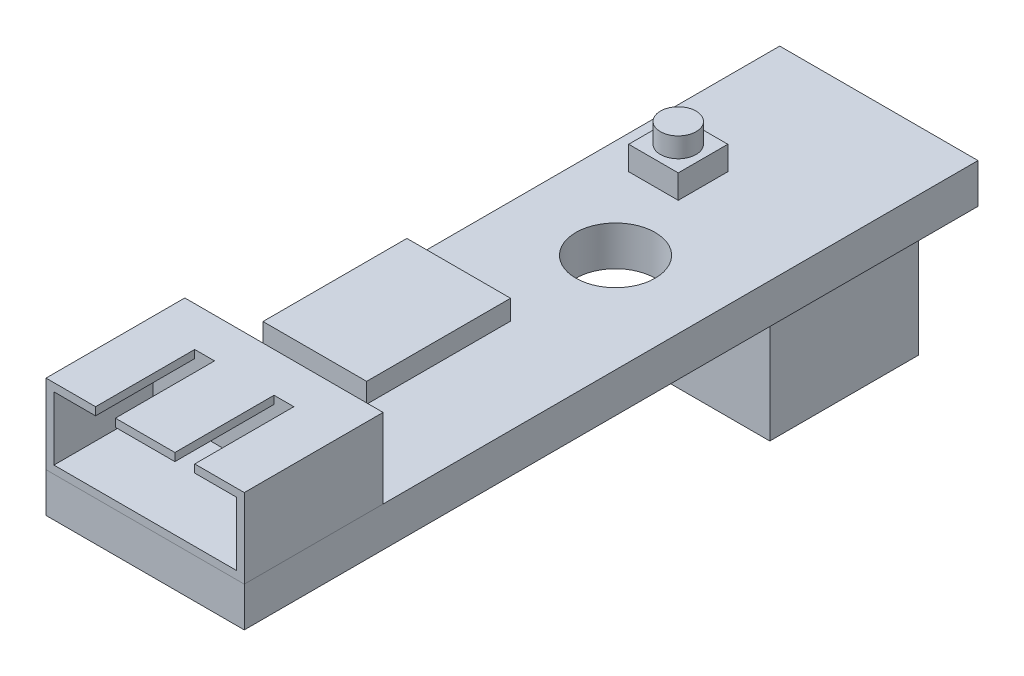
SolidWorks part; units mm, degrees
ref_plane "前视基准面" through (0, 0, 0) normal (0, 0, 1) x (1, 0, 0)
ref_plane "上视基准面" through (0, 0, 0) normal (0, 1, 0) x (1, 0, 0)
ref_plane "右视基准面" through (0, 0, 0) normal (1, 0, 0) x (0, 0, -1)
sketch "草图1" plane through (0, 0, 0) normal (0, 1, 0) x (1, 0, 0)
  line L1 (-5, 18.5) -> (5, 18.5)
  line L2 (-5, 18.5) -> (-5, -18.5)
  line L3 (-5, -18.5) -> (5, -18.5)
  line L4 (5, 18.5) -> (5, -18.5)
  line L5 (-5, 18.5) -> (5, -18.5) construction
  line L6 (-5, -18.5) -> (5, 18.5) construction
  point P0 (0, 0)
  dimension "D1" = 37
  dimension "D2" = 10
extrude "凸台-拉伸1" add sketch "草图1" along normal blind 2
sketch "草图2" plane through (0, 2, 0) normal (0, 1, 0) x (1, 0, 0)
  line L0 (-5, 18.5) -> (-5, -18.5) construction
  line L1 (-5, -11.5) -> (5, -11.5)
  line L2 (-5, -11.5) -> (-5, -18.5)
  line L3 (-5, -18.5) -> (5, -18.5)
  line L4 (5, -11.5) -> (5, -18.5)
  dimension "D1" = 7
extrude "凸台-拉伸2" add sketch "草图2" along normal blind 4 separate body
sketch "草图3" plane through (0, 0, 18.5) normal (0, 0, 1) x (1, 0, 0)
  line L4 (-5, 2) -> (5, 2)
  line L5 (5, 2) -> (5, 6)
  line L6 (5, 6) -> (-5, 6)
  line L7 (-5, 6) -> (-5, 2)
  line L8 (-5, 2) -> (5, 2) construction
  line L9 (5, 2) -> (5, 6) construction
  line L10 (5, 6) -> (-5, 6) construction
  line L11 (-5, 6) -> (-5, 2) construction
  line L12 (0, 5.6) -> (0, 7.429) construction
  line L13 (1.5, 6) -> (1.5, 5.6)
  line L14 (-2.5, 6) -> (-1.5, 6)
  line L15 (-2.5, 6) -> (-2.5, 5.6)
  line L16 (-4.6, 2.4) -> (4.6, 2.4)
  line L17 (4.6, 2.4) -> (4.6, 5.6)
  line L18 (4.6, 5.6) -> (-4.6, 5.6)
  line L19 (-4.6, 5.6) -> (-4.6, 2.4)
  line L20 (-4.6, 2.4) -> (4.6, 2.4)
  line L21 (4.6, 2.4) -> (4.6, 5.6)
  line L22 (4.6, 5.6) -> (2.5, 5.6)
  line L23 (-4.6, 5.6) -> (-4.6, 2.4)
  line L24 (-2.5, 5.6) -> (-1.5, 5.6) construction
  line L25 (-1.5, 6) -> (-1.5, 5.6)
  line L26 (2.5, 6) -> (2.5, 5.6)
  line L27 (2.5, 6) -> (1.5, 6)
  line L28 (-1.5, 5.6) -> (-2.5, 5.6) construction
  line L29 (-2.5, 5.6) -> (-4.6, 5.6)
  line L30 (2.5, 5.6) -> (1.5, 5.6) construction
  line L31 (1.5, 5.6) -> (-1.5, 5.6)
  dimension "D3" = 3
  dimension "D4" = 1
  dimension "D1" = 0
  dimension "D2" = 0.4
extrude "切除-拉伸1" cut sketch "草图3" against normal blind 5
sketch "草图4" plane through (0, 0, 0) normal (0, -1, 0) x (1, 0, 0)
  line L0 (0, 18.5) -> (0, -18.5) construction
  line L1 (-5, 18.5) -> (5, 18.5) construction
  line L2 (5, -18.5) -> (-5, -18.5) construction
  circle A0 centre (0, -5.221) radius 2
  dimension "D1" = 4
extrude "切除-拉伸2" cut sketch "草图4" against normal blind 5
sketch "草图5" plane through (0, 0, 0) normal (0, -1, 0) x (1, 0, 0)
  line L0 (5, 18.5) -> (5, -18.5) construction
  line L1 (-2, -10) -> (3, -10)
  line L2 (-3, -11) -> (-3, -17.5)
  line L3 (-3, -17.5) -> (3, -17.5)
  line L4 (3, -10) -> (3, -17.5)
  line L5 (5, -18.5) -> (-5, -18.5) construction
  line L6 (-3, -11) -> (-2, -10)
  point P0 (-3, -10)
  dimension "D1" = 6
  dimension "D2" = 7.5
  dimension "D3" = 2
  dimension "D4" = 1
extrude "凸台-拉伸3" add sketch "草图5" along normal blind 7
sketch "草图6" plane through (0, 2, 0) normal (0, 1, 0) x (1, 0, 0)
  line L0 (-5, 18.5) -> (-5, -18.5) construction
  line L1 (-5, -0.3) -> (0.2273, -0.3)
  line L2 (-5, -0.3) -> (-5, -7.5587)
  line L3 (-5, -7.5587) -> (0.2273, -7.5587)
  line L4 (0.2273, -0.3) -> (0.2273, -7.5587)
  point P6 (-5, -0.3)
extrude "凸台-拉伸4" add sketch "草图6" along normal blind 1
sketch "草图7" plane through (0, 2, 0) normal (0, 1, 0) x (1, 0, 0)
  line L1 (-3.3201, 11.7036) -> (-0.8201, 11.7036)
  line L2 (-3.3201, 11.7036) -> (-3.3201, 9.2036)
  line L3 (-3.3201, 9.2036) -> (-0.8201, 9.2036)
  line L4 (-0.8201, 11.7036) -> (-0.8201, 9.2036)
  dimension "D1" = 2.5
extrude "凸台-拉伸5" add sketch "草图7" along normal blind 1.2 separate body
sketch "草图8" plane through (0, 3.2, 0) normal (0, 1, 0) x (1, 0, 0)
  line L0 (-3.3201, 11.7036) -> (-0.8201, 9.2036) construction
  line L1 (-2.0701, 10.4536) -> (-0.8201, 11.7036) construction
  line L2 (-0.8201, 11.7036) -> (-3.3201, 11.7036) construction
  line L3 (-0.8201, 9.2036) -> (-0.8201, 11.7036) construction
  line L4 (-3.3201, 11.7036) -> (-3.3201, 9.2036) construction
  circle A0 centre (-2.0701, 10.4536) radius 0.9
  point P0 (-3.3201, 11.7036)
  point P9 (-2.105, 10.4536)
  dimension "D1" = 1.8
extrude "凸台-拉伸6" add sketch "草图8" along normal blind 1
sketch "草图9" plane through (0, -7, 0) normal (0, -1, 0) x (1, 0, 0)
  line L0 (0, -12) -> (0, -15.6) construction
  line L1 (3, -10) -> (-2, -10) construction
  circle A0 centre (0, -12) radius 1.5
  circle A1 centre (0, -15.6) radius 1.5
  dimension "D1" = 3
  dimension "D3" = 2
  dimension "D2" = 3.6
extrude "切除-拉伸3" cut sketch "草图9" against normal blind 1
ref_axis "基准轴1" through (0, -6, -12) along (0, -1, 0)
ref_plane "基准面1" through (0, 0, 0) normal (1, 0, 0) x (0, -1, 0)
sketch "草图10" plane through (0, 0, 0) normal (1, 0, 0) x (0, -1, 0)
  line L0 (6, 10.5) -> (6, 13.5) construction
  line L1 (6, 10.5) -> (6, 13.5) construction
  line L3 (6, 12) -> (6.6918, 12)
  line L5 (6, 12) -> (6, 10.5)
  spline S0 degree 2 poles (6, 10.5) (6.763, 11.0996) (6.6918, 12) knots 0 0 0 1 1 1
  point P4 (6.6964, 12)
revolve "旋转1" add sketch "草图10" angle 360 about L3
sketch "草图11" plane through (0, 0, 0) normal (1, 0, 0) x (0, -1, 0)
  line L0 (6, 14.1) -> (6, 17.1) construction
  line L1 (6, 14.1) -> (6, 15.6)
  line L2 (6, 15.6) -> (6.6997, 15.6)
  line L3 (6, 15.6) -> (6, 17.1) construction
  spline S0 degree 2 poles (6, 14.1) (6.7246, 14.6772) (6.6997, 15.6) knots 0 0 0 1 1 1
  dimension "D1" = 0.6997
revolve "旋转2" add sketch "草图11" angle 360 about L2
sketch "草图12" plane through (0, 2, 0) normal (0, 1, 0) x (1, 0, 0)
  circle A0 centre (0, 5.221) radius 3.2
  circle A1 centre (0, 5.221) radius 2 construction
  dimension "D1" = 1.2
